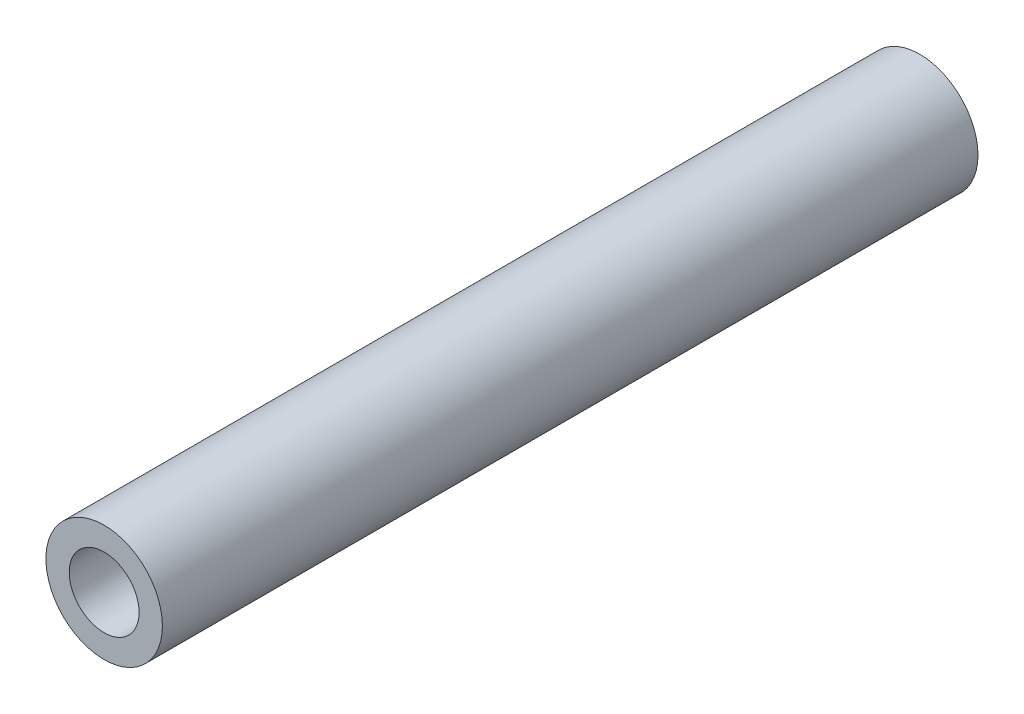
SolidWorks part; units mm, degrees
ref_plane "Спереди" through (0, 0, 0) normal (0, 0, 1) x (1, 0, 0)
ref_plane "Сверху" through (0, 0, 0) normal (0, 1, 0) x (1, 0, 0)
ref_plane "Справа" through (0, 0, 0) normal (1, 0, 0) x (0, 0, -1)
sketch "Эскиз1" plane through (0, 0, 0) normal (0, 0, 1) x (1, 0, 0)
  circle A0 centre (0, 0) radius 2.5
  circle A1 centre (0, 0) radius 1.5
  dimension "D1" = 3
  dimension "D2" = 5
extrude "тело" add sketch "Эскиз1" along normal blind 17.5 and the other way blind 17.5
